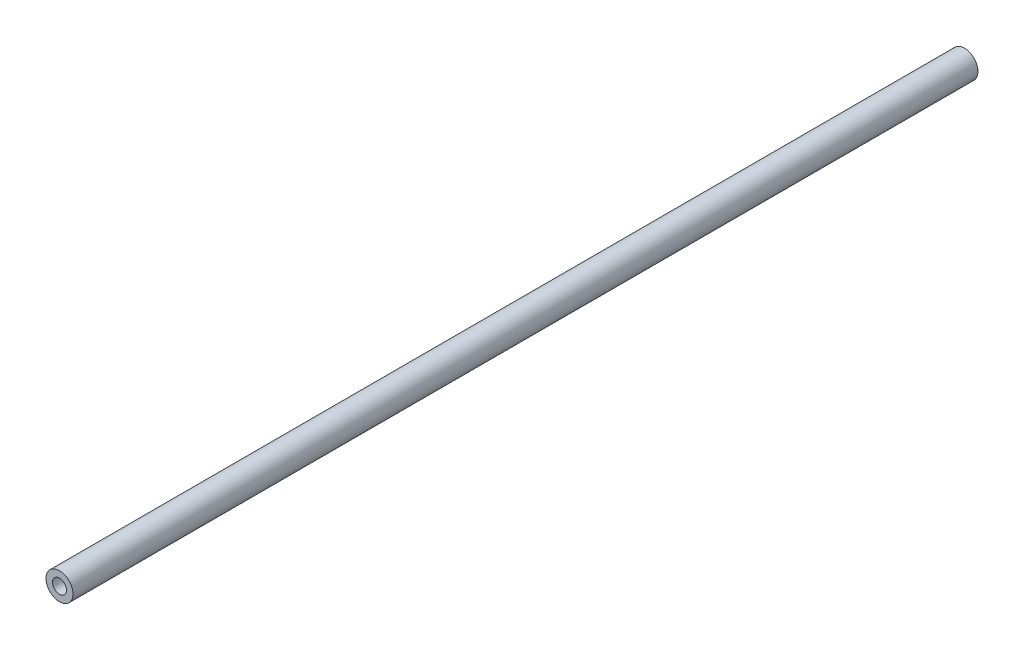
SolidWorks part; units mm, degrees
material "6061 Alloy"
ref_plane "Front Plane" through (0, 0, 0) normal (0, 0, 1) x (1, 0, 0)
ref_plane "Top Plane" through (0, 0, 0) normal (0, 1, 0) x (1, 0, 0)
ref_plane "Right Plane" through (0, 0, 0) normal (1, 0, 0) x (0, 0, -1)
sketch "Sketch1" plane through (0, 0, 0) normal (0, 0, 1) x (1, 0, 0)
  circle A0 centre (0, 0) radius 5
  dimension "D1" = 10
extrude "Boss-Extrude1" add sketch "Sketch1" along normal blind 335
hole_wizard "#6 (0.204) Diameter Hole1" positions "Sketch2" profile "Sketch3" hole size "#6" standard "ANSI Inch"
sketch "Sketch2" plane through (0, 0, 0) normal (0, 0, -1) x (-1, 0, 0)
  point P0 (0, 0)
sketch "Sketch3" plane through (0, 0, 0) normal (1, 0, 0) x (0, 1, 0)
  line L0 (0, 0) -> (0, 31.5567)
  line L1 (0, 31.5567) -> (2.5908, 30)
  line L2 (2.5908, 30) -> (2.5908, 0)
  line L5 (2.5908, 0) -> (0, 0)
  line L10 (0, 31.5567) -> (-2.5908, 30) construction
  line L11 (0, -6.35) -> (0, 107.95) construction
  dimension "Hole Dia." = 5.1816
  dimension "Hole Depth" = 30
  dimension "Drill Angle" = 118
hole_wizard "#6 (0.204) Diameter Hole2" positions "Sketch4" profile "Sketch5" hole size "#6" standard "ANSI Inch"
sketch "Sketch4" plane through (0, 0, 335) normal (0, 0, 1) x (1, 0, 0)
  point P0 (0, 0)
sketch "Sketch5" plane through (0, 0, 335) normal (1, 0, 0) x (0, -1, 0)
  line L0 (0, 0) -> (0, 31.5567)
  line L1 (0, 31.5567) -> (2.5908, 30)
  line L2 (2.5908, 30) -> (2.5908, 0)
  line L5 (2.5908, 0) -> (0, 0)
  line L10 (0, 31.5567) -> (-2.5908, 30) construction
  line L11 (0, -6.35) -> (0, 107.95) construction
  dimension "Hole Dia." = 5.1816
  dimension "Hole Depth" = 30
  dimension "Drill Angle" = 118
